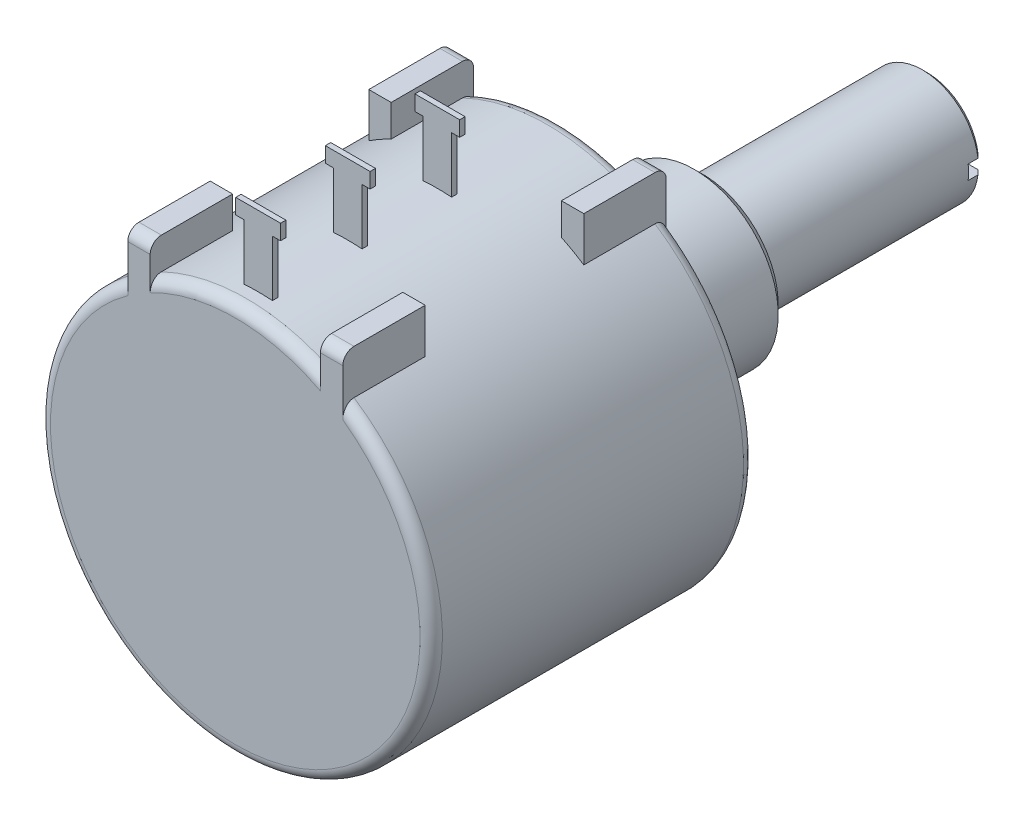
SolidWorks part; units mm, degrees
ref_plane "Front Plane" through (0, 0, 0) normal (0, 0, 1) x (1, 0, 0)
ref_plane "Top Plane" through (0, 0, 0) normal (0, 1, 0) x (1, 0, 0)
ref_plane "Right Plane" through (0, 0, 0) normal (1, 0, 0) x (0, 0, -1)
ref_plane "Plane1" through (0, 0, 0) normal (0, -1, 0) x (1, 0, 0)
sketch "Sketch1" plane through (0, 0, 0) normal (0, -1, 0) x (1, 0, 0)
  line L0 (11.1125, 18.3388) -> (0, 18.3388)
  line L1 (0, 18.3388) -> (0, 0)
  line L2 (0, 0) -> (11.1125, 0)
  line L3 (11.1125, 0) -> (11.1125, 18.3388)
  line L4 (0, 18.3388) -> (0, 0) construction
revolve "Revolve1" add sketch "Sketch1" angle 360 about L4 reverse direction yes
ref_plane "Plane2" through (0, 15.113, 0) normal (0, 1, 0) x (1, 0, 0)
sketch "Sketch2" plane through (0, 15.113, 0) normal (0, 1, 0) x (1, 0, 0)
  line L0 (0.8128, -17.0434) -> (0.8128, -16.7386)
  line L1 (0.8128, -16.7386) -> (-0.8128, -16.7386)
  line L2 (-0.8128, -16.7386) -> (-0.8128, -17.0434)
  line L3 (-0.8128, -17.0434) -> (0.8128, -17.0434)
extrude "Boss-Extrude1" add sketch "Sketch2" against normal up to next
sketch "Sketch3" plane through (0.8128, 0, 0) normal (1, 0, 0) x (0, 0, -1)
  line L0 (-17.0434, 14.2494) -> (-17.0434, 15.113)
  line L1 (-17.0434, 15.113) -> (-16.7386, 15.113)
  line L2 (-16.7386, 15.113) -> (-16.7386, 14.2494)
  line L3 (-16.7386, 14.2494) -> (-17.0434, 14.2494)
extrude "Boss-Extrude2" add sketch "Sketch3" along normal blind 0.4572
sketch "Sketch4" plane through (-0.8128, 0, 0) normal (-1, 0, 0) x (0, 0, 1)
  line L0 (17.0434, 15.113) -> (17.0434, 14.2494)
  line L1 (17.0434, 14.2494) -> (16.7386, 14.2494)
  line L2 (16.7386, 14.2494) -> (16.7386, 15.113)
  line L3 (16.7386, 15.113) -> (17.0434, 15.113)
extrude "Boss-Extrude3" add sketch "Sketch4" along normal blind 0.4572
sketch "Sketch5" plane through (0, 15.113, 0) normal (0, 1, 0) x (1, 0, 0)
  line L0 (0.8128, -11.9634) -> (0.8128, -11.6586)
  line L1 (0.8128, -11.6586) -> (-0.8128, -11.6586)
  line L2 (-0.8128, -11.6586) -> (-0.8128, -11.9634)
  line L3 (-0.8128, -11.9634) -> (0.8128, -11.9634)
extrude "Boss-Extrude4" add sketch "Sketch5" against normal up to next
sketch "Sketch6" plane through (0.8128, 0, 0) normal (1, 0, 0) x (0, 0, -1)
  line L0 (-11.9634, 14.2494) -> (-11.9634, 15.113)
  line L1 (-11.9634, 15.113) -> (-11.6586, 15.113)
  line L2 (-11.6586, 15.113) -> (-11.6586, 14.2494)
  line L3 (-11.6586, 14.2494) -> (-11.9634, 14.2494)
extrude "Boss-Extrude5" add sketch "Sketch6" along normal blind 0.4572
sketch "Sketch7" plane through (-0.8128, 0, 0) normal (-1, 0, 0) x (0, 0, 1)
  line L0 (11.9634, 15.113) -> (11.9634, 14.2494)
  line L1 (11.9634, 14.2494) -> (11.6586, 14.2494)
  line L2 (11.6586, 14.2494) -> (11.6586, 15.113)
  line L3 (11.6586, 15.113) -> (11.9634, 15.113)
extrude "Boss-Extrude6" add sketch "Sketch7" along normal blind 0.4572
sketch "Sketch8" plane through (0, 15.113, 0) normal (0, 1, 0) x (1, 0, 0)
  line L0 (0.8128, -6.8834) -> (0.8128, -6.5786)
  line L1 (0.8128, -6.5786) -> (-0.8128, -6.5786)
  line L2 (-0.8128, -6.5786) -> (-0.8128, -6.8834)
  line L3 (-0.8128, -6.8834) -> (0.8128, -6.8834)
extrude "Boss-Extrude7" add sketch "Sketch8" against normal up to next
sketch "Sketch9" plane through (0.8128, 0, 0) normal (1, 0, 0) x (0, 0, -1)
  line L0 (-6.8834, 14.2494) -> (-6.8834, 15.113)
  line L1 (-6.8834, 15.113) -> (-6.5786, 15.113)
  line L2 (-6.5786, 15.113) -> (-6.5786, 14.2494)
  line L3 (-6.5786, 14.2494) -> (-6.8834, 14.2494)
extrude "Boss-Extrude8" add sketch "Sketch9" along normal blind 0.4572
sketch "Sketch10" plane through (-0.8128, 0, 0) normal (-1, 0, 0) x (0, 0, 1)
  line L0 (6.8834, 15.113) -> (6.8834, 14.2494)
  line L1 (6.8834, 14.2494) -> (6.5786, 14.2494)
  line L2 (6.5786, 14.2494) -> (6.5786, 15.113)
  line L3 (6.5786, 15.113) -> (6.8834, 15.113)
extrude "Boss-Extrude9" add sketch "Sketch10" along normal blind 0.4572
ref_plane "Plane3" through (0, 11.811, 0) normal (0, 1, 0) x (1, 0, 0)
sketch "Sketch11" plane through (0, 11.811, 0) normal (0, 1, 0) x (1, 0, 0)
  line L0 (-4.826, -18.3388) -> (-4.826, -13.6652)
  line L1 (-4.826, -13.6652) -> (-6.096, -13.6652)
  line L2 (-6.096, -13.6652) -> (-6.096, -18.3388)
  line L3 (-6.096, -18.3388) -> (-4.826, -18.3388)
extrude "Boss-Extrude10" add sketch "Sketch11" against normal up to next
sketch "Sketch12" plane through (0, 11.811, 0) normal (0, 1, 0) x (1, 0, 0)
  line L0 (6.096, -18.3388) -> (6.096, -13.6652)
  line L1 (6.096, -13.6652) -> (4.826, -13.6652)
  line L2 (4.826, -13.6652) -> (4.826, -18.3388)
  line L3 (4.826, -18.3388) -> (6.096, -18.3388)
extrude "Boss-Extrude11" add sketch "Sketch12" against normal up to next
sketch "Sketch13" plane through (0, 11.811, 0) normal (0, 1, 0) x (1, 0, 0)
  line L0 (4.826, 0) -> (4.826, -4.6736)
  line L1 (4.826, -4.6736) -> (6.096, -4.6736)
  line L2 (6.096, -4.6736) -> (6.096, 0)
  line L3 (6.096, 0) -> (4.826, 0)
extrude "Boss-Extrude12" add sketch "Sketch13" against normal up to next
sketch "Sketch14" plane through (0, 11.811, 0) normal (0, 1, 0) x (1, 0, 0)
  line L0 (-6.096, 0) -> (-6.096, -4.6736)
  line L1 (-6.096, -4.6736) -> (-4.826, -4.6736)
  line L2 (-4.826, -4.6736) -> (-4.826, 0)
  line L3 (-4.826, 0) -> (-6.096, 0)
extrude "Boss-Extrude13" add sketch "Sketch14" against normal up to next
sketch "Sketch15" plane through (0, 0, 0) normal (0, 0, -1) x (-1, 0, 0)
  circle A0 centre (0, 0) radius 6.35
extrude "Boss-Extrude14" add sketch "Sketch15" along normal blind 0.254
sketch "Sketch16" plane through (0, 0, -0.254) normal (0, 0, -1) x (-1, 0, 0)
  circle A0 centre (0, 0) radius 4.7625
extrude "Boss-Extrude15" add sketch "Sketch16" along normal blind 7.9375
sketch "Sketch17" plane through (0, 0, -8.1915) normal (0, 0, -1) x (-1, 0, 0)
  circle A0 centre (0, 0) radius 3.175
extrude "Boss-Extrude16" add sketch "Sketch17" along normal blind 12.6873
sketch "Sketch18" plane through (0, 0, -20.8788) normal (0, 0, -1) x (-1, 0, 0)
  line L0 (3.1489, 0.4064) -> (-3.1489, 0.4064)
  arc A0 (-3.1489, 0.4064) -> (3.1489, 0.4064) centre (0, 0) ccw
extrude "Cut-Extrude1" cut sketch "Sketch18" against normal blind 0.8128
sketch "Sketch19" plane through (0, 0, -20.066) normal (0, 0, -1) x (-1, 0, 0)
  line L0 (-3.1489, -0.4064) -> (3.1489, -0.4064)
  arc A0 (3.1489, -0.4064) -> (-3.1489, -0.4064) centre (0, 0) cw
extrude "Boss-Extrude17" add sketch "Sketch19" along normal blind 0.8128
chamfer "Chamfer1" distance 0.254 angle 45 2 edges at (0, 3.175, -20.8788) (0, -3.175, -20.8788)
chamfer "Chamfer2" distance 0.508 angle 45 1 edges at (-4.7625, 0, -8.1915)
fillet "Fillet1" radius 0.635 8 edges at (0, -11.1125, 0) (0, 11.1125, 18.3388) (0, 11.1125, 0) (-5.461, 11.811, 18.3388) (0, -11.1125, 18.3388) (5.461, 11.811, 18.3388) (-5.461, 11.811, 0) (5.461, 11.811, 0) tangent propagation no
